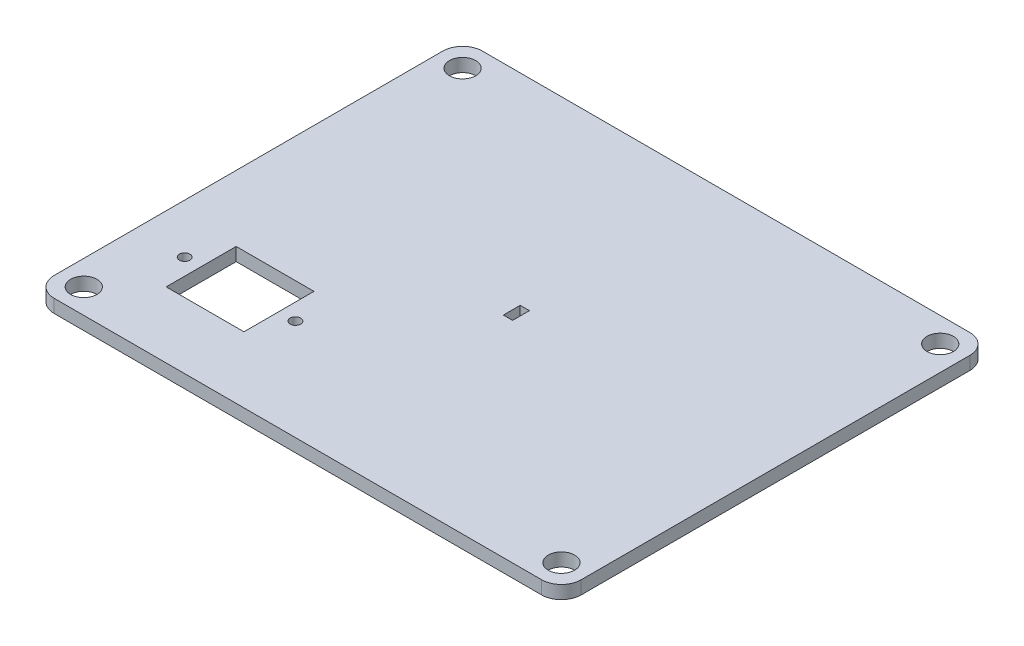
SolidWorks part; units mm, degrees
ref_plane "Front Plane" through (0, 0, 0) normal (0, 0, 1) x (1, 0, 0)
ref_plane "Top Plane" through (0, 0, 0) normal (0, 1, 0) x (1, 0, 0)
ref_plane "Right Plane" through (0, 0, 0) normal (1, 0, 0) x (0, 0, -1)
sketch "Sketch1" plane through (0, 0, 0) normal (0, 1, 0) x (1, 0, 0)
  line L1 (0, 0) -> (203.2, 0)
  line L2 (0, 0) -> (0, -165.1)
  line L3 (0, -165.1) -> (203.2, -165.1)
  line L4 (203.2, 0) -> (203.2, -165.1)
extrude "Boss-Extrude1" add sketch "Sketch1" along normal blind 5.08
ref_axis "Axis1" through (101.6, 5.08, 165.1) along (0, 0, -1)
ref_axis "Axis2" through (0, 5.08, 82.55) along (1, 0, 0)
ref_plane "Plane3" through (0, 0, 82.55) normal (0, 0, 1) x (1, 0, 0)
ref_plane "Plane4" through (101.6, 0, 0) normal (-1, 0, 0) x (0, 0, 1)
sketch "Sketch3" plane through (0, 5.08, 0) normal (0, 1, 0) x (1, 0, 0)
  circle A0 centre (9.525, -9.525) radius 5.08
extrude "Cut-Extrude1" cut sketch "Sketch3" against normal blind 5.08
mirror "Mirror1" about plane through (101.6, 0, 0) normal (-1, 0, 0) of "Cut-Extrude1"
mirror "Mirror2" about plane through (0, 0, 82.55) normal (0, 0, 1) of "Mirror1"
sketch "Sketch4" plane through (0, 0, 0) normal (0, -1, 0) x (-1, 0, 0)
  text T0 "Ben Phung & Joaquin Gonzalez-Salgado"
extrude "Cut-Extrude2" cut sketch "Sketch4" against normal blind 0.254
fillet "Fillet1" radius 7.62 4 edges at (203.2, 2.54, 165.1) (0, 2.54, 165.1) (0, 2.54, 0) (203.2, 2.54, 0)
sketch "Sketch5" plane through (0, 5.08, 0) normal (0, 1, 0) x (1, 0, 0)
  line L0 (0, -7.62) -> (0, -157.48) construction
  line L1 (99.822, -77.5958) -> (103.378, -77.5958)
  line L2 (99.822, -77.5958) -> (99.822, -84.0982)
  line L3 (99.822, -84.0982) -> (103.378, -84.0982)
  line L4 (103.378, -77.5958) -> (103.378, -84.0982)
  dimension "D1" = 99.822
extrude "Cut-Extrude3" cut sketch "Sketch5" against normal blind 5.08
sketch "Sketch6" plane through (0, 5.08, 0) normal (0, 1, 0) x (1, 0, 0)
  line L0 (0, -7.62) -> (0, -157.48) construction
  line L1 (25.4, -112.7001) -> (55.3999, -112.7001)
  line L2 (25.4, -112.7001) -> (25.4, -139.7)
  line L3 (25.4, -139.7) -> (55.3999, -139.7)
  line L4 (55.3999, -112.7001) -> (55.3999, -139.7)
  line L5 (7.62, -165.1) -> (195.58, -165.1) construction
  dimension "D1" = 25.4
  dimension "D2" = 25.4
extrude "Cut-Extrude4" cut sketch "Sketch6" against normal blind 5.08
sketch "Sketch7" plane through (0, 5.08, 0) normal (0, 1, 0) x (1, 0, 0)
  line L0 (25.4, -112.7001) -> (25.4, -139.7) construction
  line L1 (55.3999, -139.7) -> (55.3999, -112.7001) construction
  circle A0 centre (19.05, -126.2) radius 2.032
  circle A1 centre (61.7499, -126.2) radius 2.032
  point P6 (0, 0)
  dimension "D1" = 6.35
  dimension "D2" = 6.35
extrude "Cut-Extrude5" cut sketch "Sketch7" against normal blind 5.08
